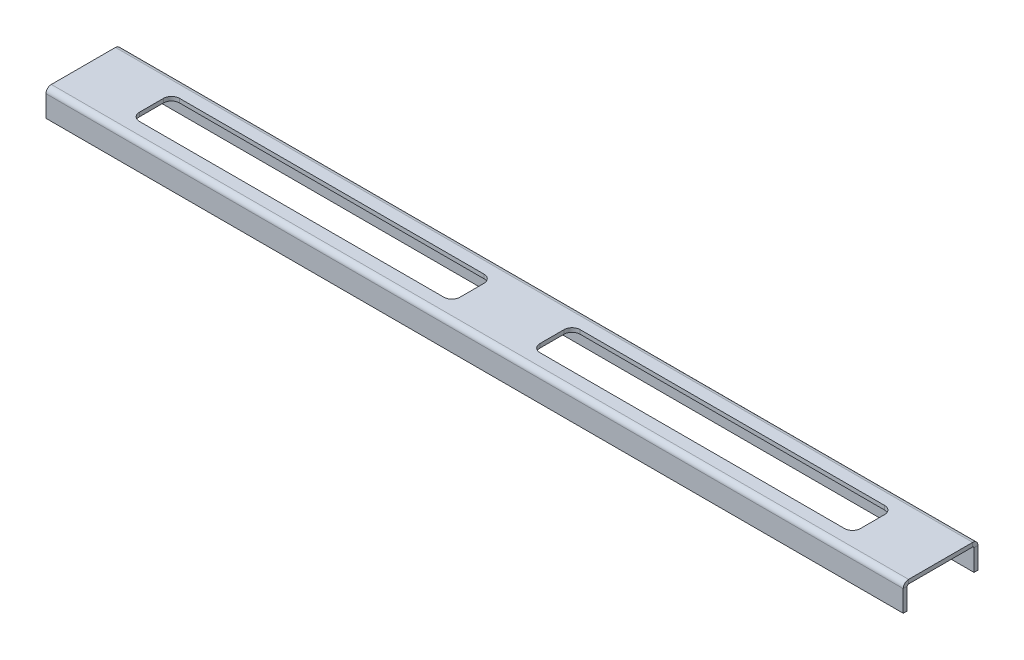
SolidWorks part; units mm, degrees
note: The reader was unsure of these and kept them because the rebuilt part matched: thickness of "基体-法兰1", "边线-法兰1", "边线-法兰2", "钣金6", "钣金7", "钣金8", "钣金14", "钣金15", "钣金16"; flange length of "边线-法兰1", "边线-法兰2".
material "普通碳钢"
ref_plane "前视基准面" through (0, 0, 0) normal (0, 0, 1) x (1, 0, 0)
ref_plane "上视基准面" through (0, 0, 0) normal (0, 1, 0) x (1, 0, 0)
ref_plane "右视基准面" through (0, 0, 0) normal (1, 0, 0) x (0, 0, -1)
sketch "草图1" plane through (0, 0, 0) normal (0, 0, 1) x (1, 0, 0)
  line L1 (-160.5, 30) -> (160.5, 30)
  line L2 (-160.5, 30) -> (-160.5, -30)
  line L3 (-160.5, -30) -> (160.5, -30)
  line L4 (160.5, 30) -> (160.5, -30)
  line L5 (-160.5, 30) -> (160.5, -30) construction
  line L6 (-160.5, -30) -> (160.5, 30) construction
  point P0 (0, 0)
  dimension "D1" = 321
  dimension "D2" = 60
base flange "基体-法兰1" sketch "草图1" thickness 1.5 reverse thickness direction no parameters "D1"=0.5
edge flange "边线-法兰1" sketch "草图10" flange profiles "草图10", "草图11" flange angle 90 flange length 28 flange position material inside bend radius 0.5 thickness 1.5 parameters "D1"=1, "D6"=10, "D8"=1
sketch "草图10" plane through (0, 30, 0) normal (0, 1, 0) x (-1, 0, 0)
  line L2 (-160.5, 0) -> (-160.5, 26.5)
  line L3 (-160.5, 26.5) -> (160.5, 26.5)
  line L4 (160.5, 26.5) -> (160.5, 0)
  line L5 (-160.5, 0) -> (160.5, 0) construction
  line L6 (-160.5, 0) -> (160.5, 0)
sketch "草图11" plane through (0, -30, 0) normal (0, -1, 0) x (1, 0, 0)
  line L0 (-160.5, 0) -> (160.5, 0) construction
  line L1 (-160.5, 0) -> (160.5, 0)
  line L2 (-160.5, 0) -> (-160.5, 26.5)
  line L3 (-160.5, 26.5) -> (160.5, 26.5)
  line L4 (160.5, 26.5) -> (160.5, 0)
bend "边线折弯1" bend radius 0.5 bend angle 90 parameters "D5"=1
bend "边线折弯2" bend radius 0.5 bend angle 90 parameters "D5"=2
edge flange "边线-法兰2" sketch "草图16" flange profiles "草图16", "草图17" flange angle 90 flange length 10 flange position material inside bend radius 0.5 thickness 1.5 parameters "D1"=1, "D6"=10, "D8"=1
sketch "草图16" plane through (0, 28.5, 26.5) normal (0, 0, -1) x (1, 0, 0)
  line L1 (160.5, 0) -> (-160.5, 0) construction
  line L2 (-160.5, 0) -> (-160.5, 8.5)
  line L3 (-160.5, 8.5) -> (160.5, 8.5)
  line L4 (160.5, 8.5) -> (160.5, 0)
  line L5 (160.5, 0) -> (-160.5, 0)
sketch "草图17" plane through (0, -28.5, 26.5) normal (0, 0, -1) x (-1, 0, 0)
  line L0 (160.5, 0) -> (-160.5, 0) construction
  line L1 (160.5, 0) -> (-160.5, 0)
  line L2 (160.5, 0) -> (160.5, 8.5)
  line L3 (160.5, 8.5) -> (-160.5, 8.5)
  line L4 (-160.5, 8.5) -> (-160.5, 0)
bend "边线折弯3" bend radius 0.5 bend angle 90 parameters "D5"=3
bend "边线折弯4" bend radius 0.5 bend angle 90 parameters "D5"=4
sketch "草图19" plane through (0, 30, 0) normal (0, 1, 0) x (1, 0, 0)
  line L0 (0, 36.0868) -> (0, -45.539) construction
  line L1 (-160.5, 1.5) -> (160.5, 1.5) construction
  line L2 (-132, -5) -> (-18, -5)
  line L3 (-135, -8) -> (-135, -17)
  line L4 (-132, -20) -> (-18, -20)
  line L5 (-15, -8) -> (-15, -17)
  line L6 (-135, -5) -> (-15, -20) construction
  line L7 (-135, -20) -> (-15, -5) construction
  arc A0 (-18, -5) -> (-15, -8) centre (-18, -8) cw
  arc A1 (-15, -17) -> (-18, -20) centre (-18, -17) cw
  arc A2 (-132, -20) -> (-135, -17) centre (-132, -17) cw
  arc A3 (-135, -8) -> (-132, -5) centre (-132, -8) cw
  point P3 (-75, -12.5)
  dimension "D5" = 3
  dimension "D1" = 120
  dimension "D2" = 15
  dimension "D3" = 14
  dimension "D4" = 75
extrude "切除-拉伸2" cut sketch "草图19" against normal through all normal cut yes
mirror "镜向1" about plane through (0, 0, 0) normal (1, 0, 0) of "切除-拉伸2"
sketch "草图20" plane through (0, 0, 0) normal (0, 0, 1) x (1, 0, 0)
  line L1 (-180.5875, -54.9106) -> (160.5, -54.9106)
  line L2 (-180.5875, -54.9106) -> (-180.5875, 20)
  line L3 (-180.5875, 20) -> (160.5, 20)
  line L4 (160.5, -54.9106) -> (160.5, 20)
extrude "切除-拉伸3" cut sketch "草图20" along normal blind 57 and the other way blind 10 normal cut yes
sketch "折弯-线1" [suppressed] plane through (0, 0, 0) normal (0, 1, 0) x (-1, 0, 0)
sketch "边界框1" [suppressed] plane through (0, 0, 0) normal (0, 1, 0) x (-1, 0, 0)
sheet metal parameters "钣金6" thickness 1.5 parameters "D1"=0.5, "D7"=1
flat pattern "平板型式6" [suppressed]
sketch "折弯-线2" plane through (0, 0, 0) normal (0, 1, 0) x (-1, 0, 0)
sketch "边界框2" [suppressed] plane through (0, 0, 0) normal (0, 1, 0) x (-1, 0, 0)
sheet metal parameters "钣金7" thickness 1.5 parameters "D1"=0.5, "D7"=1
flat pattern "平板型式6" [suppressed]
sketch "折弯-线2" plane through (0, 0, 0) normal (0, 1, 0) x (-1, 0, 0)
sketch "边界框2" [suppressed] plane through (0, 0, 0) normal (0, 1, 0) x (-1, 0, 0)
bend of the flat pattern "展开-<边线折弯1>1"
bend of the flat pattern "展开-<边线折弯2>1"
sheet metal parameters "钣金8" thickness 1.5 parameters "D1"=0.5, "D7"=1
flat pattern "平板型式6" [suppressed]
sketch "折弯-线2" plane through (0, 0, 0) normal (0, 1, 0) x (-1, 0, 0)
sketch "边界框2" [suppressed] plane through (0, 0, 0) normal (0, 1, 0) x (-1, 0, 0)
bend of the flat pattern "展开-<边线折弯1>1"
bend of the flat pattern "展开-<边线折弯2>1"
bend of the flat pattern "展开-<边线折弯3>1"
bend of the flat pattern "展开-<边线折弯4>1"
sheet metal parameters "钣金14" thickness 1.5 parameters "D1"=0.5, "D7"=1
flat pattern "平板型式6"
sketch "折弯-线2" plane through (0, 0, 0) normal (0, 0, 1) x (1, 0, 0)
  line L0 (-168, -55.45) -> (168, -55.45) construction
  line L1 (168, 55.45) -> (-168, 55.45) construction
  line L2 (-168, -29.15) -> (168, -29.15) construction
  line L3 (168, 29.15) -> (-168, 29.15) construction
  line L4 (-168, -55.45) -> (168, -55.45) construction
  line L5 (168, 55.45) -> (-168, 55.45) construction
  line L6 (-168, -29.15) -> (168, -29.15) construction
  line L7 (168, 29.15) -> (-168, 29.15) construction
sketch3d "边界框2" [suppressed]
  line L0 (-168, -64.6, 0) -> (168, -64.6, 0) construction
  line L1 (-168, 64.6, 0) -> (168, 64.6, 0) construction
  line L2 (-168, -64.6, 0) -> (-168, 64.6, 0) construction
  line L3 (168, -64.6, 0) -> (168, 64.6, 0) construction
bend of the flat pattern "展开-<边线折弯1>1"
bend of the flat pattern "展开-<边线折弯2>1"
bend of the flat pattern "展开-<边线折弯3>1"
bend of the flat pattern "展开-<边线折弯4>1"
sheet metal parameters "钣金15" thickness 1.5 parameters "D1"=0.5, "D7"=1
flat pattern "平板型式6"
sketch "折弯-线2" plane through (0, 0, 0) normal (0, 0, 1) x (1, 0, 0)
  line L0 (-168, -55.45) -> (168, -55.45) construction
  line L1 (168, 55.45) -> (-168, 55.45) construction
  line L2 (-168, -29.15) -> (168, -29.15) construction
  line L3 (168, 29.15) -> (-168, 29.15) construction
  line L4 (-168, -55.45) -> (168, -55.45) construction
  line L5 (168, 55.45) -> (-168, 55.45) construction
  line L6 (-168, -29.15) -> (168, -29.15) construction
  line L7 (168, 29.15) -> (-168, 29.15) construction
sketch3d "边界框2" [suppressed]
  line L0 (-168, -64.6, 0) -> (168, -64.6, 0) construction
  line L1 (-168, 64.6, 0) -> (168, 64.6, 0) construction
  line L2 (-168, -64.6, 0) -> (-168, 64.6, 0) construction
  line L3 (168, -64.6, 0) -> (168, 64.6, 0) construction
bend of the flat pattern "展开-<边线折弯1>1"
bend of the flat pattern "展开-<边线折弯2>1"
bend of the flat pattern "展开-<边线折弯3>1"
bend of the flat pattern "展开-<边线折弯4>1"
sheet metal parameters "钣金16" thickness 1.5 parameters "D1"=0.5, "D7"=1
flat pattern "平板型式6" [suppressed]
sketch "折弯-线2" plane through (0, 0, 0) normal (0, 0, 1) x (1, 0, 0)
  line L0 (-168, -55.45) -> (168, -55.45) construction
  line L1 (168, 55.45) -> (-168, 55.45) construction
  line L2 (-168, -29.15) -> (168, -29.15) construction
  line L3 (168, 29.15) -> (-168, 29.15) construction
  line L4 (-168, -55.45) -> (168, -55.45) construction
  line L5 (168, 55.45) -> (-168, 55.45) construction
  line L6 (-168, -29.15) -> (168, -29.15) construction
  line L7 (168, 29.15) -> (-168, 29.15) construction
sketch3d "边界框2" [suppressed]
  line L0 (-168, -64.6, 0) -> (168, -64.6, 0) construction
  line L1 (-168, 64.6, 0) -> (168, 64.6, 0) construction
  line L2 (-168, -64.6, 0) -> (-168, 64.6, 0) construction
  line L3 (168, -64.6, 0) -> (168, 64.6, 0) construction
bend of the flat pattern "展开-<边线折弯3>1"
bend of the flat pattern "展开-<边线折弯1>1"
